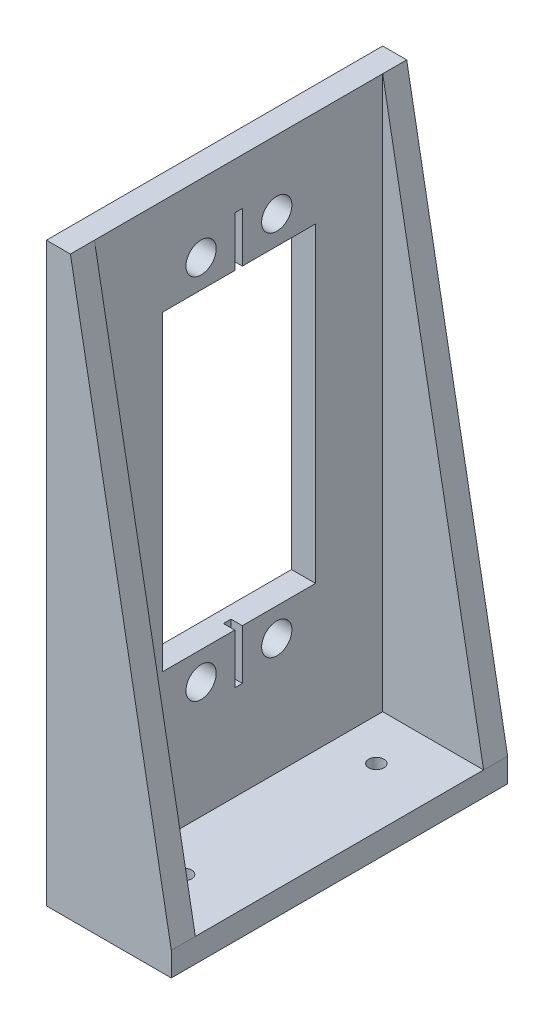
SolidWorks part; units mm, degrees
ref_plane "Front Plane" through (0, 0, 0) normal (0, 0, 1) x (1, 0, 0)
ref_plane "Top Plane" through (0, 0, 0) normal (0, 1, 0) x (1, 0, 0)
ref_plane "Right Plane" through (0, 0, 0) normal (1, 0, 0) x (0, 0, -1)
sketch "Sketch1" plane through (0, 0, 0) normal (0, 0, 1) x (1, 0, 0)
  line L0 (0, 0) -> (0, 76.2)
  line L1 (0, 76.2) -> (3.175, 76.2)
  line L2 (3.175, 76.2) -> (3.175, 3.175)
  line L3 (3.175, 3.175) -> (16.51, 3.175)
  line L4 (16.51, 3.175) -> (16.51, 0)
  line L5 (16.51, 0) -> (0, 0)
  dimension "D1" = 3.175
  dimension "D2" = 3.175
  dimension "D3" = 16.51
  dimension "D4" = 76.2
extrude "Boss-Extrude1" add sketch "Sketch1" along normal mid plane 44.45
sketch "Sketch3" plane through (0, 0, 22.225) normal (0, 0, 1) x (1, 0, 0)
  line L0 (3.175, 76.2) -> (16.51, 3.175)
  line L1 (16.51, 3.175) -> (3.175, 3.175)
  line L2 (3.175, 3.175) -> (3.175, 76.2)
extrude "Boss-Extrude2" add sketch "Sketch3" against normal blind 3.175
mirror "Mirror1" about plane through (0, 0, 0) normal (0, 0, 1) of "Boss-Extrude2"
sketch "Sketch4" plane through (0, 3.175, 0) normal (0, 1, 0) x (1, 0, 0)
  line L1 (3.175, 19.05) -> (16.51, 19.05) construction
  line L3 (3.175, 0) -> (16.51, 0) construction
  line L4 (3.175, -19.05) -> (3.175, 19.05) construction
  line L5 (16.51, -19.05) -> (16.51, 19.05) construction
  circle A0 centre (8.68, 12.7) radius 1
  circle A3 centre (8.68, -12.7) radius 1
  dimension "D1" = 2
  dimension "D2" = 6.35
  dimension "D3" = 5.505
extrude "Cut-Extrude2" cut sketch "Sketch4" against normal through all
sketch "Sketch5" plane through (3.175, 0, 0) normal (1, 0, 0) x (0, 0, -1)
  line L0 (-19.05, 76.2) -> (-19.05, 3.175) construction
  line L1 (-19.05, 3.175) -> (19.05, 3.175) construction
  circle A0 centre (-4.953, 18.575) radius 2
  circle A1 centre (5.047, 18.575) radius 2
  circle A2 centre (-4.953, 67.175) radius 2
  circle A3 centre (5.047, 67.175) radius 2
  dimension "D3" = 4
  dimension "D5" = 4
  dimension "D7" = 4
  dimension "D8" = 4
  dimension "D1" = 14.097
  dimension "D2" = 15.4
  dimension "D4" = 10
  dimension "D6" = 48.6
extrude "Cut-Extrude3" cut sketch "Sketch5" against normal through all
sketch "Sketch6" plane through (3.175, 0, 0) normal (1, 0, 0) x (0, 0, -1)
  line L0 (-10.08, 63.452) -> (10.174, 22.298) construction
  line L1 (-10.08, 63.452) -> (10.174, 63.452)
  line L2 (-10.08, 63.452) -> (-10.08, 22.298)
  line L3 (-10.08, 22.298) -> (10.174, 22.298)
  line L4 (10.174, 63.452) -> (10.174, 22.298)
  line L5 (10.174, 63.452) -> (-10.08, 22.298) construction
  line L6 (-4.953, 67.175) -> (5.047, 18.575) construction
  line L7 (-4.953, 18.575) -> (5.047, 67.175) construction
  point P12 (0.047, 42.875)
  point P13 (0.047, 42.875)
  dimension "D1" = 41.154
  dimension "D2" = 20.254
extrude "Cut-Extrude4" cut sketch "Sketch6" against normal through all
sketch "Sketch7" plane through (0, 63.452, 0) normal (0, -1, 0) x (1, 0, 0)
  line L0 (3.175, -10.174) -> (3.175, 10.08) construction
  line L1 (1.675, -0.5) -> (3.175, -0.5)
  line L2 (1.675, -0.5) -> (1.675, 0.5)
  line L3 (1.675, 0.5) -> (3.175, 0.5)
  line L4 (3.175, -0.5) -> (3.175, 0.5)
  line L5 (1.675, -0.5) -> (3.175, 0.5) construction
  line L6 (1.675, 0.5) -> (3.175, -0.5) construction
  line L7 (9.0805, 0) -> (-9.0805, 0) construction
  point P0 (2.425, 0)
  dimension "D1" = 1
  dimension "D2" = 1.5
extrude "Cut-Extrude5" cut sketch "Sketch7" against normal blind 6.604
extrude "Cut-Extrude6" cut sketch "Sketch7<2>" along normal blind 6.604 from surface starting at face at (1.5875, 22.298, -0.047)
sketch "Sketch7<2>" plane through (0, 63.452, 0) normal (0, -1, 0) x (1, 0, 0) same geometry as "Sketch7"
equation "\"D1@Sketch4\"=2mm"
equation "\"tightTol\" = 0.005in"
equation "\"normTol\"= 0.01in"
equation "\"looseTol\"= 0.02in"
equation "\"D2@Sketch5\"=0.5in+2.7mm"
equation "\"D3@Sketch5\"=4mm"
equation "\"D4@Sketch5\"=10mm"
equation "\"D5@Sketch5\"=4mm"
equation "\"D6@Sketch5\"=48.6mm"
equation "\"D8@Sketch5\"=4mm"
equation "\"D1@Sketch6\" = 40.9mm + \"normTol\""
equation "\"D2@Sketch6\" = 20mm + \"normTol\""
equation "\"D1@Sketch7\"=1mm"
equation "\"D2@Sketch7\"=1.5mm"
equation "\"D7@Sketch5\"=4mm"
equation "\"D3@Sketch4\"=0.125000in+2.33mm"
